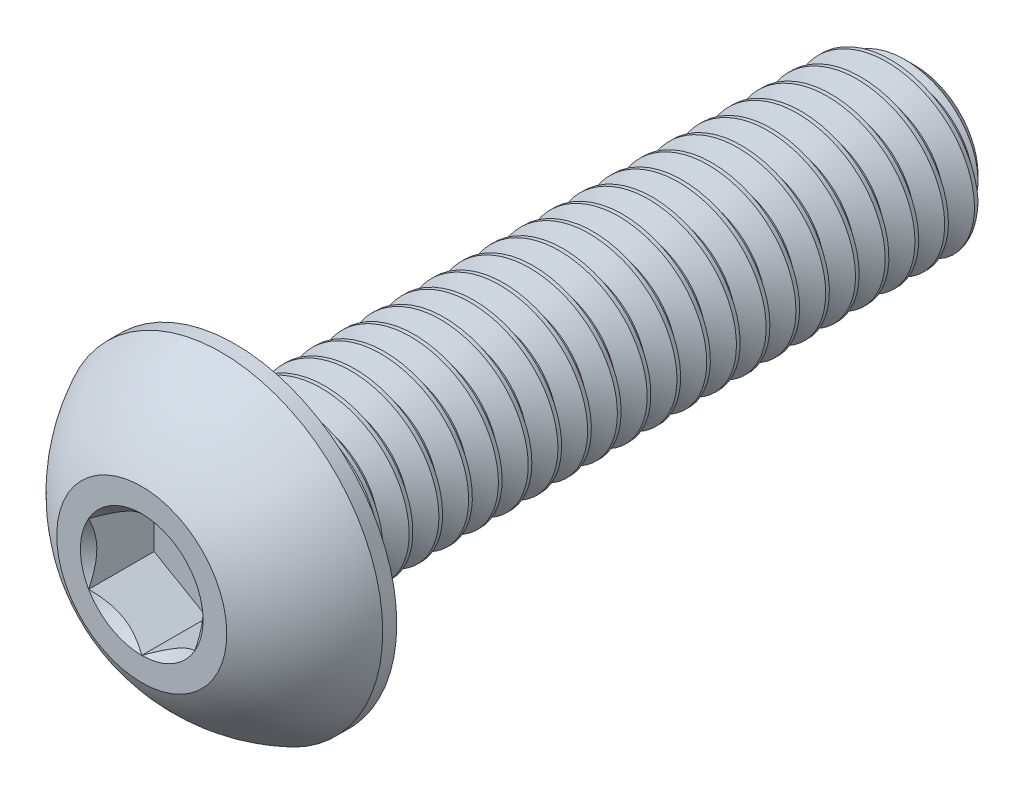
SolidWorks part; units mm, degrees
ref_plane "Front" through (0, 0, 0) normal (0, 0, 1) x (1, 0, 0)
ref_plane "Top" through (0, 0, 0) normal (0, 1, 0) x (1, 0, 0)
ref_plane "Right" through (0, 0, 0) normal (1, 0, 0) x (0, 0, -1)
sketch "Sketch1" plane through (0, 0, 0) normal (1, 0, 0) x (0, 0, -1)
  line L2 (2.2, 2) -> (18.2, 2)
  line L3 (18.2, 2) -> (18.2, 0)
  line L4 (18.2, 0) -> (2.2, 0)
  line L6 (1.87, 3.8) -> (2.2, 3.8) construction
  line L7 (18.2, 2) -> (18.2, -2) construction
  line L8 (0, 0) -> (2.2, 0) construction
  line L9 (2.2, 3.8) -> (2.2, -3.8) construction
  line L11 (2.2, 2) -> (2.2, 0)
  line L13 (0, 1.25) -> (0, -1.25) construction
  line L14 (0, 1.25) -> (0, 2) construction
  line L15 (18.2, -2) -> (17.5, -2) construction
  arc A3 (0, 2) -> (1.87, 3.8) centre (3.7264, 0) cw construction
  dimension "D1" = 0.33
  dimension "Pitch" = 0.7
revolve "Revolve1" add sketch "Sketch1" angle 360 mid plane about L4
sketch "Sketch7" plane through (0, 0, 0) normal (1, 0, 0) x (0, 0, -1)
  line L6 (1.87, 3.8) -> (2.2, 3.8) construction
  line L8 (0, 0) -> (2.2, 0) construction
  line L11 (2.2, 3.8) -> (2.2, -3.8) construction
  line L12 (1.87, 3.8) -> (2.2, 3.8)
  line L13 (0, 0) -> (2.2, 0)
  line L14 (0, 1.25) -> (0, -1.25) construction
  line L15 (2.2, 3.8) -> (2.2, 0)
  line L16 (0, 2) -> (0, 0)
  arc A2 (1.87, 3.8) -> (0, 2) centre (3.7264, 0) ccw construction
  arc A3 (1.87, 3.8) -> (0, 2) centre (3.7264, 0) ccw
revolve "Revolve2" add sketch "Sketch7" angle 360 mid plane about L13
sketch "Sketch5" plane through (0, 0, 0) normal (0, 0, 1) x (1, 0, 0)
  line L1 (1.25, -0.7217) -> (1.25, 0.7217)
  line L2 (1.25, 0.7217) -> (0, 1.4434)
  line L3 (0, 1.4434) -> (-1.25, 0.7217)
  line L4 (-1.25, 0.7217) -> (-1.25, -0.7217)
  line L5 (-1.25, -0.7217) -> (0, -1.4434)
  line L6 (0, -1.4434) -> (1.25, -0.7217)
  circle A0 centre (0, 0) radius 1.25 construction
extrude "Cut-Extrude2" cut sketch "Sketch5" against normal blind 1.54
sketch "Sketch6" plane through (0, 0, 0) normal (0, 0, 1) x (1, 0, 0)
  circle A0 centre (0, 0) radius 1.4434
extrude "Cut-Extrude3" cut sketch "Sketch6" against normal blind 1.54 draft 45
sketch "Sketch11" plane through (0, 0, 0) normal (1, 0, 0) x (0, 0, -1)
  line L0 (2.2, -3.8) -> (2.2, 3.8)
  point P4 (2.2, 0)
split "Split1" trim tools "Sketch11" bodies to split 113 resulting bodies 119 120
sketch "Sketch10" plane through (0, 0, 0) normal (1, 0, 0) x (0, 0, -1)
  line L0 (18.2, 2) -> (18.2, -2) construction
  point P0 (17.15, -2)
  dimension "D1" = 1.05
sketch "Sketch3" plane through (0, 0, -18.2) normal (0, 0, -1) x (-1, 0, 0)
  circle A0 centre (0, 0) radius 2
curve "Helix/Spiral1" pitch 0.7 height 16.7 turns 23.8571
sketch "Sketch2" plane through (0, 0, 0) normal (1, 0, 0) x (0, 0, -1)
  line L0 (18.1562, 2.0758) -> (18.8563, 2.0758) construction
  line L1 (18.8563, 2.0758) -> (18.5063, 1.4696) construction
  line L2 (18.5063, 1.4696) -> (18.1562, 2.0758) construction
  line L3 (18.5063, 2.0758) -> (18.5063, 2) construction
  line L4 (18.5063, 2) -> (18.5063, 1.5453) construction
  line L5 (18.5063, 1.5453) -> (18.5063, 1.4696) construction
  line L6 (18.4625, 1.5453) -> (18.55, 1.5453)
  line L7 (18.2, 2) -> (18.8125, 2) construction
  line L8 (18.1781, 2.0379) -> (18.8344, 2.0379)
  line L9 (18.1781, 2.0379) -> (18.4625, 1.5453)
  line L10 (18.8344, 2.0379) -> (18.55, 1.5453)
  point P10 (18.5063, 1.5453)
  point P13 (18.5063, 2)
  point P16 (18.5063, 2.0379)
  dimension "D1" = 0.7
  dimension "D2" = 0.0875
chamfer "Chamfer1" distance 0.525 angle 45 1 edges at (0, 2, -18.2)
sweep "Cut-Sweep1" cut profiles "Sketch2" path "Helix/Spiral1" align with end faces yes
combine bodies "Combine1" operation type add bodies to combine 120 114
equation "\"D3@Helix/Spiral1\" = \"Lg@Sketch1\" + \"D4@Helix/Spiral1\""
equation "\"D1@Chamfer1\" = \"D4@Helix/Spiral1\" * .75"
equation "\"D1@Cut-Extrude2\" = \"Head Ht@Sketch1\" * .7"
equation "\"D1@Sketch1\" = \"Head Ht@Sketch1\" * .15"
equation "\"D1@Sketch10\" = \"D4@Helix/Spiral1\" * 1.5"
equation "\"D1@Cut-Extrude3\" = \"D1@Cut-Extrude2\""
equation "\"D4@Helix/Spiral1\"=\"Pitch@Sketch1\""
equation "\"D1@Sketch2\"=\"Pitch@Sketch1\""
equation "\"D2@Sketch2\"=\"D1@Sketch2\"/8"
